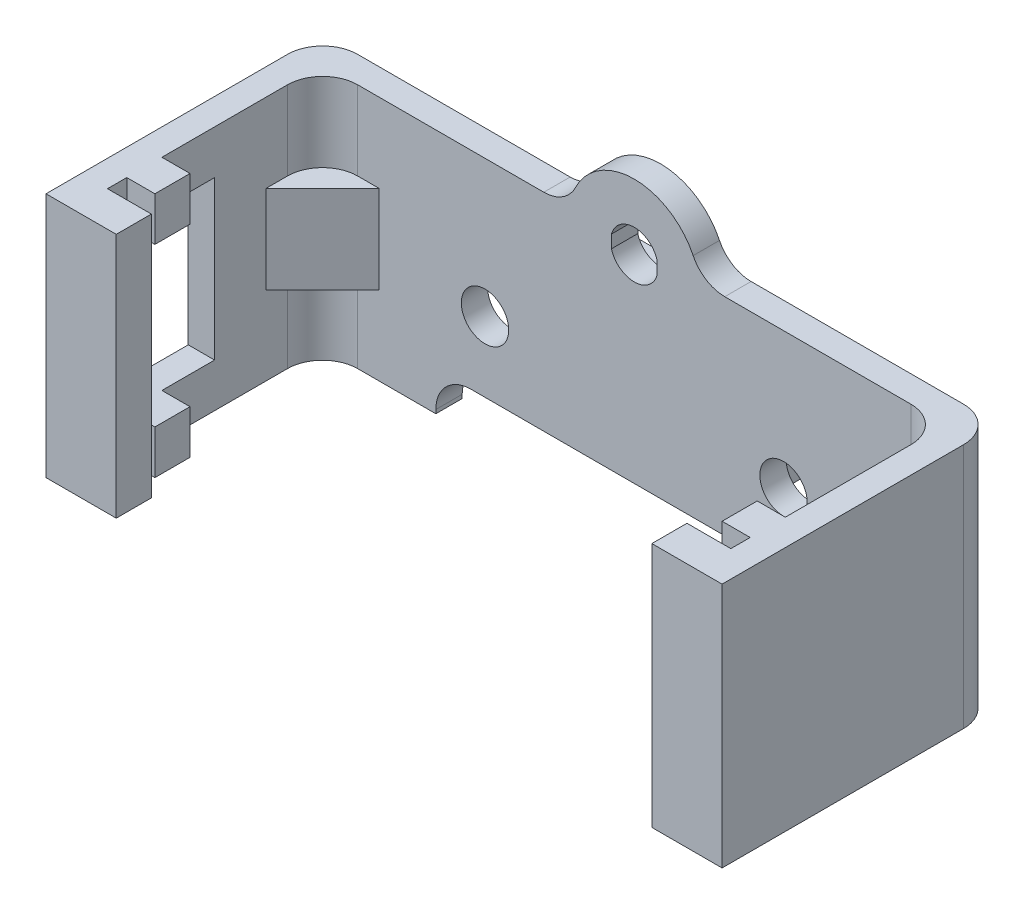
SolidWorks part; units mm, degrees
ref_plane "前视基准面" through (0, 0, 0) normal (0, 0, 1) x (1, 0, 0)
ref_plane "上视基准面" through (0, 0, 0) normal (0, 1, 0) x (1, 0, 0)
ref_plane "右视基准面" through (0, 0, 0) normal (1, 0, 0) x (0, 0, -1)
sketch "草图1" plane through (0, 0, 0) normal (0, 0, 1) x (1, 0, 0)
  line L1 (-13.5, -8.5) -> (13.5, -8.5)
  line L2 (-13.5, -8.5) -> (-13.5, 8.5)
  line L3 (-13.5, 8.5) -> (13.5, 8.5)
  line L4 (13.5, -8.5) -> (13.5, 8.5)
  line L5 (-13.5, -8.5) -> (13.5, 8.5) construction
  line L6 (-13.5, 8.5) -> (13.5, -8.5) construction
  point P0 (0, 0)
  dimension "D1" = 27
  dimension "D2" = 17
extrude "凸台-拉伸1" add sketch "草图1" along normal blind 1
sketch "草图2" plane through (0, 0, 1) normal (0, 0, 1) x (1, 0, 0)
  line L0 (-8.27, 4.125) -> (8.27, 4.125) construction
  line L3 (0, 1.575) -> (0, -1.575) construction
  line L4 (8.27, 4.125) -> (8.27, -4.125) construction
  line L5 (8.27, -4.125) -> (-8.27, -4.125) construction
  line L6 (-8.27, -4.125) -> (-8.27, 4.125) construction
  circle A0 centre (0, 4.125) radius 2.55
  circle A1 centre (0, -4.125) radius 2.55
  circle A2 centre (8.27, 4.125) radius 2.55
  circle A3 centre (8.27, -4.125) radius 2.55
  circle A4 centre (-8.27, 4.125) radius 2.55
  circle A5 centre (-8.27, -4.125) radius 2.55
  point P2 (0, 1.575)
  point P5 (0, -1.575)
  point P6 (0, 0)
  point P11 (-2.55, 4.125)
  point P20 (-5.72, 4.125)
  dimension "D1" = 5.1
  dimension "D4" = 3.17
  dimension "D2" = 3.15
extrude "切除-拉伸1" cut sketch "草图2" against normal through all
sketch "草图3" plane through (0, -8.5, 0) normal (0, -1, 0) x (1, 0, 0)
  line L0 (13.5, 0) -> (19, 0)
  line L1 (13.5, 1) -> (13.5, 0)
  line L2 (20.5, 1) -> (13.5, 1)
  line L3 (20.5, 1) -> (20.5, -30)
  line L4 (-13.5, 1) -> (-13.5, 0) construction
  line L5 (19, -28.5) -> (19, 0)
  line L6 (-13.5, -28.5) -> (-13.5, -30)
  line L7 (-13.5, -30) -> (20.5, -30)
  line L9 (-13.5, -28.5) -> (19, -28.5)
  dimension "D1" = 7
  dimension "D2" = 1.5
  dimension "D3" = 1.5
  dimension "D4" = 30
extrude "凸台-拉伸2" add sketch "草图3" against normal up to surface (17 mm away) up to face at (0, 8.5, 0.5)
sketch "草图6" plane through (0, 0, 0) normal (0, 1, 0) x (1, 0, 0)
  line L0 (19, 0) -> (19, 5)
  line L1 (19, 28.5) -> (19, 0) construction
  line L2 (19, 5) -> (14, 0)
  line L3 (19, 0) -> (-13.5, 0) construction
  line L4 (14, 0) -> (19, 0)
  line L5 (19, 28.5) -> (14, 28.5)
  line L6 (-13.5, 28.5) -> (19, 28.5) construction
  line L7 (14, 28.5) -> (19, 23.5)
  line L8 (19, 23.5) -> (19, 28.5)
  line L9 (20.5, 30) -> (-13.5, 30) construction
  line L10 (19, 19) -> (17.5, 19)
  line L11 (19, 19) -> (19, 21)
  line L12 (19, 21) -> (17.5, 21)
  line L13 (17.5, 19) -> (17.5, 21)
  point P18 (17.5, 20)
  dimension "D1" = 5
  dimension "D2" = 5
  dimension "D3" = 5
  dimension "D4" = 5
  dimension "D5" = 10
  dimension "D6" = 1.5
  dimension "D7" = 2
extrude "凸台-拉伸3" add sketch "草图6" along normal mid plane 4
chamfer "倒角1" distance 1 angle 45 1 edges at (-13.5, 0, 0)
sketch "草图8" plane through (0, 0, 0) normal (0, 0, -1) x (-1, 0, 0)
  circle A0 centre (0, 0) radius 2
  dimension "D1" = 4
extrude "切除-拉伸4" cut sketch "草图8" against normal up to next
fillet "圆角1" radius 3 6 edges at (20.5, 0, -30) (20.5, 0, 1) (19, 5.25, 0) (19, -5.25, 0) (19, 5.25, -28.5) (19, -5.25, -28.5)
sketch "草图9" plane through (0, 0, -30) normal (0, 0, -1) x (-1, 0, 0)
  line L1 (-3.5, 13) -> (3.5, 13)
  line L2 (-3.5, 13) -> (-3.5, 0)
  line L3 (-3.5, 0) -> (3.5, 0)
  line L4 (3.5, 13) -> (3.5, 0)
  point P4 (0, 0)
  dimension "D1" = 7
  dimension "D2" = 13
extrude "凸台-拉伸4" add sketch "草图9" against normal up to surface (1.5 mm away) up to face at (8.125, 0, -28.5)
sketch "草图7" plane through (0, 0, -30) normal (0, 0, -1) x (-1, 0, 0)
  line L0 (0, 0) -> (0, 10) construction
  line L1 (-8.5, 2.7) -> (8.5, 2.7) construction
  circle A0 centre (0, 0) radius 1.35 construction
  circle A1 centre (0, 10) radius 1.35
  circle A3 centre (-8.5, 2.7) radius 1.35
  circle A4 centre (8.5, 2.7) radius 1.35
  point P9 (0, 2.7)
  dimension "D1" = 2.7
  dimension "D5" = 2.7
  dimension "D6" = 2.7
  dimension "D2" = 10
  dimension "D3" = 2.7
  dimension "D4" = 17
extrude "切除-拉伸5" cut sketch "草图7" against normal blind 10
sketch "草图11" plane through (0, 0, -30) normal (0, 0, -1) x (-1, 0, 0)
  line L2 (13.5, 0) -> (-17.5, 0)
  line L3 (13.5, 8.5) -> (13.5, -8.5) construction
  line L4 (-17.5, 8.5) -> (-17.5, -8.5) construction
  line L5 (-17.5, 0) -> (-17.5, -8.5)
  line L6 (-17.5, -8.5) -> (13.5, -8.5)
  line L7 (13.5, -8.5) -> (13.5, 0)
  arc A1 (-17.5, -8.5) -> (-9, 0) centre (-9, -8.5) cw
  line M4 (13.5, -8.5) -> (13.5, 8.5)
  line M16 (-17.5, -8.5) -> (13.5, -8.5)
extrude "切除-拉伸6" cut sketch "草图11" against normal up to next contours A1 L2 M16 M4 region at (1.1496, -4.397, -30)
fillet "圆角2" radius 2.2 6 edges at (-13.5, 8.5, -29.25) (-3.5, 8.5, -29.25) (3.5, 8.5, -29.25) (-3.5, 13, -29.25) (3.5, 13, -29.25) (-13.5, 0, -29.25)
sketch "草图13" plane through (0, 0, -30) normal (0, 0, -1) x (-1, 0, 0)
  line L0 (11.3, 0) -> (-9, 0) construction
  line L1 (-11.2, 5.4) -> (-5.8, 5.4)
  line L2 (-11.2, 5.4) -> (-11.2, 0)
  line L3 (-11.2, 0) -> (-5.8, 0)
  line L4 (-5.8, 5.4) -> (-5.8, 0)
  line L5 (-11.2, 5.4) -> (-5.8, 0) construction
  line L6 (-11.2, 0) -> (-5.8, 5.4) construction
  line L11 (11.2, 0) -> (5.8, 0)
  line L12 (11.2, 0) -> (11.2, 5.4)
  line L18 (-5.8, 5.4) -> (5.8, 5.4)
  line L19 (11.2, 5.4) -> (5.8, 5.4)
  line L20 (5.8, 0) -> (5.8, 5.4)
  line L21 (11.2, 0) -> (5.8, 5.4) construction
  line L22 (11.2, 5.4) -> (5.8, 0) construction
  line L23 (-5.8, 5.4) -> (-5.8, 0)
  line L24 (-5.8, 0) -> (5.8, 0)
  line L25 (5.8, 5.4) -> (5.8, 0)
  point P0 (-8.5, 2.7)
  point P6 (8.5, 2.7)
  point P12 (0.1939, 2.7)
  line M20 (-9, 0) -> (11.3, 0)
extrude "凸台-拉伸6" add sketch "草图13" along normal blind 4 contours L20 L18 L4 M20 region at (0, 2.7, -30)
sketch "草图14" plane through (0, 8.5, 0) normal (0, 1, 0) x (1, 0, 0)
  line L0 (-1.3, 28.5) -> (1.3, 28.5) construction
  line L1 (-13.5, 34) -> (13.5, 34)
  line L2 (-13.5, 34) -> (-13.5, 28.5)
  line L3 (-13.5, 28.5) -> (13.5, 28.5)
  line L4 (13.5, 34) -> (13.5, 28.5)
  line L5 (-3.5, 28.5) -> (-1.3, 28.5) construction
  line L6 (5.8, 34) -> (-5.8, 34) construction
  line L7 (-13.5, 28.5) -> (-13.5, 30) construction
  point P5 (0, 28.5)
  point P8 (0, 28.5)
extrude "切除-拉伸7" cut sketch "草图14" against normal through all both and the other way through all flip side to cut
sketch "草图15" plane through (0, 0, 0) normal (0, -1, 0) x (1, 0, 0)
  line L0 (-11.3, -30) -> (-5.8, -30) construction
  line L1 (-19.25, -30) -> (19.25, -30)
  line L2 (-19.25, -30) -> (-19.25, -14.25)
  line L3 (-19.25, -14.25) -> (19.25, -14.25)
  line L4 (19.25, -30) -> (19.25, -14.25)
  line L5 (-17.75, -14.25) -> (17.75, -14.25)
  line L6 (-17.75, -14.25) -> (-17.75, -28.5)
  line L7 (-17.75, -28.5) -> (17.75, -28.5)
  line L8 (17.75, -14.25) -> (17.75, -28.5)
  line L9 (-11.3, -28.5) -> (9, -28.5) construction
  line L10 (0, -14.25) -> (0, -34) construction
  line L11 (5.8, -34) -> (-5.8, -34) construction
  line L12 (13.5, -28.5) -> (13.5, -30)
  line L13 (-17.75, -17.35) -> (-16.15, -17.35)
  line L14 (-17.75, -17.35) -> (-17.75, -19.35)
  line L15 (-17.75, -19.35) -> (-16.15, -19.35)
  line L16 (-16.15, -17.35) -> (-16.15, -19.35)
  line L17 (-17.75, -14.25) -> (-15.25, -14.25)
  line L18 (-17.75, -14.25) -> (-17.75, -16.25)
  line L19 (-17.75, -16.25) -> (-15.25, -16.25)
  line L20 (-15.25, -14.25) -> (-15.25, -16.25)
  line L21 (15.25, -14.25) -> (17.75, -14.25)
  line L22 (15.25, -14.25) -> (15.25, -16.25)
  line L23 (15.25, -16.25) -> (17.75, -16.25)
  line L24 (17.75, -14.25) -> (17.75, -16.25)
  line L25 (16.15, -17.35) -> (17.75, -17.35)
  line L26 (16.15, -17.35) -> (16.15, -19.35)
  line L27 (16.15, -19.35) -> (17.75, -19.35)
  line L28 (17.75, -17.35) -> (17.75, -19.35)
  line L29 (13.5, -30) -> (13.5, -28.5) construction
  point P17 (0, -14.25)
  line M27 (-11.3, -28.5) -> (-11.3, -30)
  line M33 (9, -30) -> (9, -28.5)
  dimension "D2" = 1.5
  dimension "D3" = 1.1
  dimension "D4" = 1.6
  dimension "D5" = 1.6
  dimension "D6" = 2
  dimension "D7" = 2.5
  dimension "D8" = 2
  dimension "D9" = 12.25
  dimension "D10" = 2.5
  dimension "D11" = 38.5
extrude "凸台-拉伸7" add sketch "草图15" against normal blind 10.5 and the other way blind 3.5 contours L3 L8 L7 L1 L4 M33 | L20 L3 L6 L19 | L16 L13 L6 L15 | L7 L6 L3 L2 L1 M27 | L22 L23 L8 L3 | L26 L27 L28 L25 region at (-19.0736, 0, -22.125) region at (-16.5, 0, -15.25) region at (17.8891, 0, -23.6391) region at (-16.95, 0, -18.35) region at (16.5, 0, -15.25)
sketch "草图16" plane through (0, 8.5, 0) normal (0, 1, 0) x (1, 0, 0)
  line L0 (-1.3, 30) -> (-1.3, 28.5)
  line L1 (-11.3, 30) -> (13.5, 30)
  line L2 (-11.3, 30) -> (-11.3, 28.5)
  line L3 (-11.3, 28.5) -> (13.5, 28.5)
  line L4 (13.5, 30) -> (13.5, 28.5)
  line L6 (1.3, 30) -> (1.3, 28.5)
  line M5 (-5.7, 30) -> (-11.3, 30)
  line M6 (-11.3, 30) -> (-11.3, 28.5)
  line M7 (-11.3, 28.5) -> (-5.7, 28.5)
  line M8 (-5.7, 28.5) -> (-5.7, 30)
extrude "凸台-拉伸8" add sketch "草图16" along normal up to surface (2 mm away) contours M8 M5 M6 M7 | L3 L0 L1 M8 | L1 L6 L3 L4 region at (-3.5, 8.5, -29.25) region at (-8.5, 8.5, -29.25) region at (7.4, 8.5, -29.25) up to face at (-16.2417, 10.5, -20.95)
ref_plane "基准面1" through (0, 3.5, 0) normal (0, -1, 0) x (-1, 0, 0)
sketch "草图17" plane through (0, 3.5, 0) normal (0, -1, 0) x (-1, 0, 0)
  line L0 (17.75, 25.275) -> (14.525, 28.5)
  line L1 (17.75, 19.35) -> (17.75, 28.5) construction
  line L2 (17.75, 28.5) -> (11.3, 28.5) construction
  line L3 (14.525, 28.5) -> (17.75, 28.5)
  line L4 (17.75, 28.5) -> (17.75, 25.275)
  line L5 (-17.75, 25.275) -> (-17.75, 28.5)
  line L6 (-17.75, 19.35) -> (-17.75, 28.5) construction
  line L7 (-17.75, 28.5) -> (-14.525, 28.5)
  line L8 (-13.5, 28.5) -> (-17.75, 28.5) construction
  line L9 (-14.525, 28.5) -> (-17.75, 25.275)
extrude "凸台-拉伸9" add sketch "草图17" along normal mid plane 5
sketch "草图18" plane through (-19.25, 0, 0) normal (-1, 0, 0) x (0, 0, 1)
  line L0 (-17.35, -3.5) -> (-17.35, 10.5) construction
  line L1 (-17.35, 8) -> (-22.35, 8)
  line L2 (-17.35, 8) -> (-17.35, -1)
  line L3 (-17.35, -1) -> (-22.35, -1)
  line L4 (-22.35, 8) -> (-22.35, -1)
  line L5 (-14.25, -3.5) -> (-14.25, 10.5) construction
  point P8 (-22.35, 3.5)
  point P9 (-14.25, 3.5)
  dimension "D1" = 9
  dimension "D2" = 5
extrude "切除-拉伸8" cut sketch "草图18" against normal up to surface (37 mm away) up to face at (17.75, 3.5, -16.8)
sketch "草图19" plane through (0, 0, -28.5) normal (0, 0, 1) x (1, 0, 0)
  line L1 (-11.3, 0) -> (13.5, 0)
  line L2 (-11.3, 0) -> (-11.3, -1.2889)
  line L3 (-11.3, -1.2889) -> (13.5, -1.2889)
  line L4 (13.5, 0) -> (13.5, -1.2889)
  circle A0 centre (0, 10) radius 3.7264
  arc A1 (3.5, 10.8) -> (1.3, 13) centre (1.3, 10.8) ccw construction
  circle A2 centre (0, 10) radius 1.35
  arc A3 (-1.3, 9.636) -> (1.3, 9.636) centre (0, 10) ccw construction
extrude "凸台-拉伸10" add sketch "草图19" against normal up to surface (1.5 mm away) up to face at (0, 10, -30)
fillet "圆角4" radius 2 11 edges at (3.6927, 10.5, -29.25) (-3.6927, 10.5, -29.25) (19.25, 3.5, -30) (-19.25, 3.5, -30) (-11.3, -1.2889, -29.25) (13.5, -1.2889, -29.25) (17.75, -1.25, -28.5) (17.75, 8.25, -28.5) (-17.75, 8.25, -28.5) (-17.75, -1.25, -28.5) (0, 0, -30)
